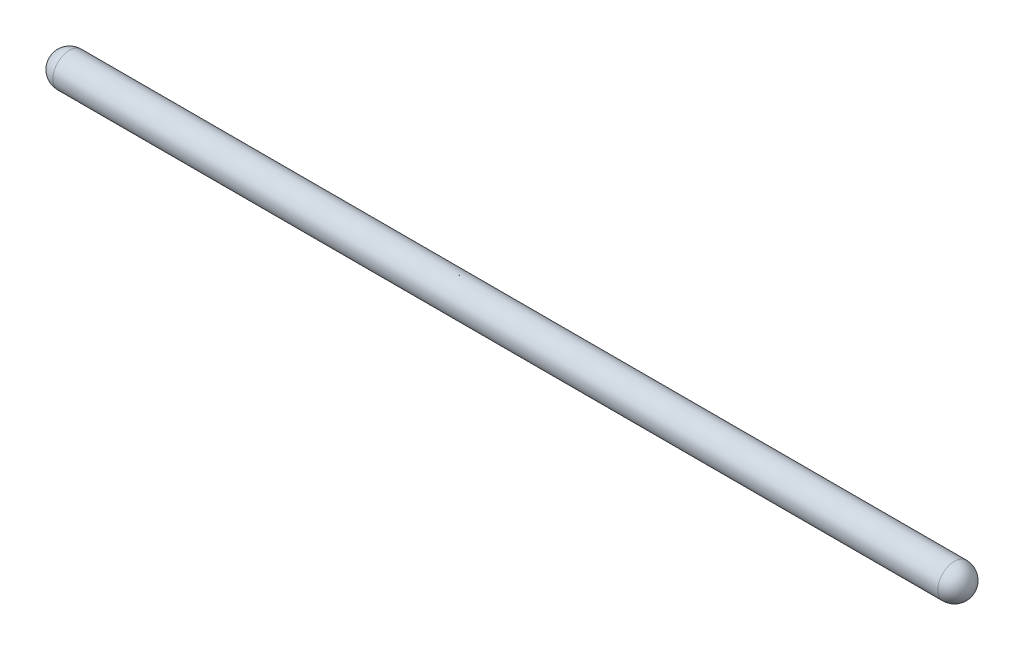
SolidWorks part; units mm, degrees
material "Brass"
ref_plane "Front Plane" through (0, 0, 0) normal (0, 0, 1) x (1, 0, 0)
ref_plane "Top Plane" through (0, 0, 0) normal (0, 1, 0) x (1, 0, 0)
ref_plane "Right Plane" through (0, 0, 0) normal (1, 0, 0) x (0, 0, -1)
sketch "Sketch1" plane through (0, 0, 0) normal (0, 0, 1) x (1, 0, 0)
  line L0 (0, 0) -> (165, 0) construction
  line L1 (3, 3) -> (162, 3)
  line L2 (165, 0) -> (0, 0)
  arc A0 (165, 0) -> (162, 3) centre (162, 0) ccw
  arc A1 (3, 3) -> (0, 0) centre (3, 0) ccw
revolve "Revolve1" add sketch "Sketch1" angle 360 about L0
